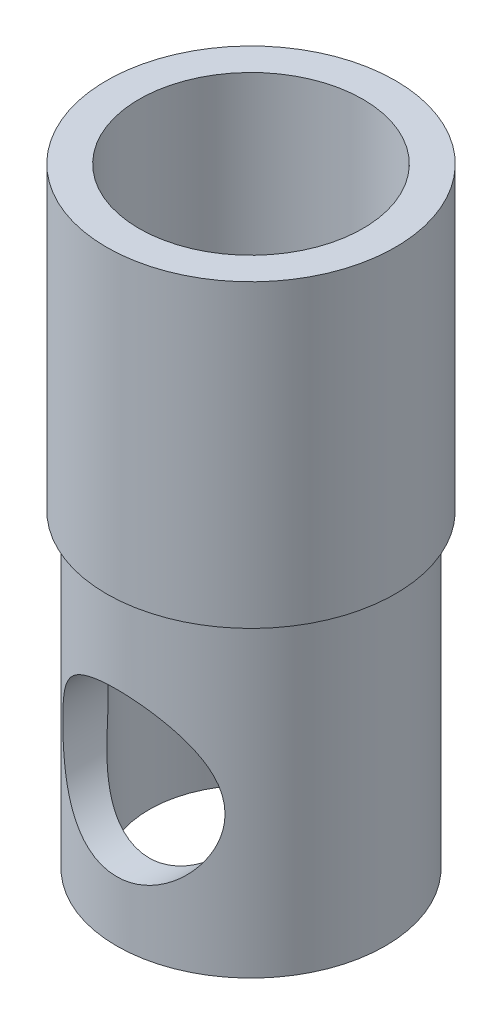
SolidWorks part; units mm, degrees
material "PTFE (general)"
ref_plane "Front Plane" through (0, 0, 0) normal (0, 0, 1) x (1, 0, 0)
ref_plane "Top Plane" through (0, 0, 0) normal (0, 1, 0) x (1, 0, 0)
ref_plane "Right Plane" through (0, 0, 0) normal (1, 0, 0) x (0, 0, -1)
sketch "Sketch1" plane through (0, 0, 0) normal (0, 1, 0) x (1, 0, 0)
  circle A0 centre (0, 0) radius 8.28
  circle A1 centre (0, 0) radius 6.28
  dimension "D1" = 16.56
  dimension "D2" = 12.56
extrude "Boss-Extrude1" add sketch "Sketch1" along normal blind 1 and the other way blind 18.1
sketch "Sketch2" plane through (0, 1, 0) normal (0, 1, 0) x (1, 0, 0)
  circle A0 centre (0, 0) radius 8.9
  circle A1 centre (0, 0) radius 6.9
  dimension "D1" = 17.8
  dimension "D2" = 13.8
extrude "Boss-Extrude2" add sketch "Sketch2" along normal blind 18.5
sketch "Sketch3" plane through (0, 0, 0) normal (0, 0, 1) x (1, 0, 0)
  line L0 (-8.28, -18.1) -> (8.28, -18.1) construction
  circle A0 centre (0, -9.4) radius 5
  dimension "D1" = 10
  dimension "D2" = 8.7
extrude "Cut-Extrude1" cut sketch "Sketch3" along normal through all
